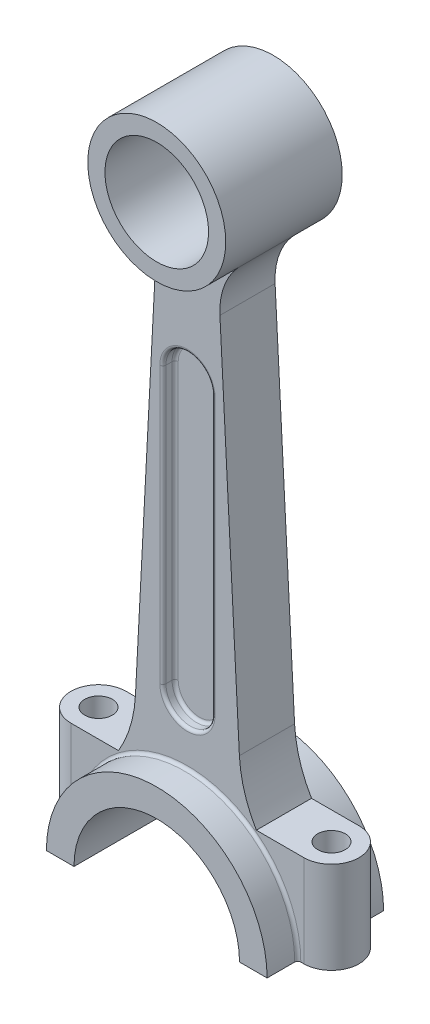
SolidWorks part; units mm, degrees
material "AISI 4340 Steel, normalized"
ref_plane "Front Plane" through (0, 0, 0) normal (0, 0, 1) x (1, 0, 0)
ref_plane "Top Plane" through (0, 0, 0) normal (0, 1, 0) x (1, 0, 0)
ref_plane "Right Plane" through (0, 0, 0) normal (1, 0, 0) x (0, 0, -1)
sketch "Sketch1" plane through (0, 0, 0) normal (0, 0, 1) x (1, 0, 0)
  line L0 (0, -201.2) -> (0, 0) construction
  line L1 (-17.8497, -169.9368) -> (-10, -20.1556)
  line L2 (17.8497, -169.9368) -> (10, -20.1556)
  line L3 (27, -201.2) -> (36, -201.2)
  line L4 (36, -201.2) -> (27, -201.2)
  line L5 (0, -201.2) -> (-36, -201.2)
  circle A4 centre (0, 0) radius 22.5
  circle A5 centre (0, 0) radius 16.9
  arc A6 (27, -201.2) -> (-27, -201.2) centre (0, -201.2) ccw
  arc A7 (36, -201.2) -> (-36, -201.2) centre (0, -201.2) ccw
  dimension "D1" = 33.8
  dimension "D2" = 45
  dimension "D3" = 72
  dimension "D4" = 54
  dimension "D5" = 201.2
  dimension "D6" = 20
  dimension "D7" = 6
extrude "Boss-Extrude1" add sketch "Sketch1" along normal mid plane 38 contours A4 A5 | L0 A6 L3 A7 | A6 L0 A7 L5 region at (-20.1899, -181.0101, 0) region at (20.1899, -181.0101, 0) region at (-4.9903, -21.2865, 0)
extrude "Boss-Extrude2" add sketch "Sketch1<3>" along normal mid plane 18 contours A7 L0 A4 L1 | L0 A7 L2 A4 region at (-7.1843, -100.8455, 0) region at (7.1843, -100.8455, 0)
sketch "Sketch1<3>" plane through (0, 0, 0) normal (0, 0, 1) x (1, 0, 0) same geometry as "Sketch1"
sketch "Sketch2" plane through (0, 0, 9) normal (0, 0, 1) x (1, 0, 0)
  line L0 (0, -55.5604) -> (0, -145.5604) construction
  line L1 (8, -55.5604) -> (8, -145.5604)
  line L2 (-8, -55.5604) -> (-8, -145.5604)
  arc A0 (8, -55.5604) -> (-8, -55.5604) centre (0, -55.5604) ccw
  arc A1 (-8, -145.5604) -> (8, -145.5604) centre (0, -145.5604) ccw
  point P3 (0, -100.5604)
  dimension "D2" = 8
  dimension "D1" = 90
extrude "Cut-Extrude1" cut sketch "Sketch2" against normal blind 4
mirror "Mirror1" about plane through (0, 0, 0) normal (0, 0, 1) of "Cut-Extrude1"
fillet "Fillet2" radius 1 16 edges at (0, -153.5604, 9) (-8, -100.5604, 9) (0, -47.5604, 9) (0, -153.5604, -9) (-8, -100.5604, -9) (0, -47.5604, -9) (8, -100.5604, 5) (0, -153.5604, 5) (-8, -100.5604, 5) (0, -47.5604, 5) (-8, -100.5604, -5) (0, -153.5604, -5) (8, -100.5604, -5) (0, -47.5604, -5) (8, -100.5604, 9) (8, -100.5604, -9)
fillet "Fillet3" radius 22.5 2 edges at (10, -20.1556, 0) (-10, -20.1556, 0)
fillet "Fillet4" radius 40 2 edges at (-17.8497, -169.9368, 0) (17.8497, -169.9368, 0)
ref_plane "Plane2" through (0, -171.2, 0) normal (0, -1, 0) x (-1, 0, 0)
sketch "Sketch3" plane through (0, -171.2, 0) normal (0, -1, 0) x (-1, 0, 0)
  line L0 (38, 0) -> (-38, 0) construction
  line L1 (38, -9) -> (-38, -9)
  line L2 (38, 9) -> (-38, 9)
  arc A0 (38, -9) -> (38, 9) centre (38, 0) ccw
  arc A1 (-38, 9) -> (-38, -9) centre (-38, 0) ccw
  circle A2 centre (-38, 0) radius 4.5
  circle A3 centre (38, 0) radius 4.5
  point P2 (0, 0)
  dimension "D2" = 9
  dimension "D3" = 9
  dimension "D4" = 9
  dimension "D1" = 76
extrude "Boss-Extrude3" add sketch "Sketch3" along normal up to surface (30 mm away) up to face at (-31.5, -201.2, 0)
sketch "Sketch4" plane through (0, 0, -9) normal (0, 0, -1) x (-1, 0, 0)
  line L1 (-27, -201.2) -> (27, -201.2)
  line L2 (-27, -201.2) -> (27, -201.2)
  arc A1 (27, -201.2) -> (-27, -201.2) centre (0, -201.2) ccw
  arc A2 (27, -201.2) -> (-27, -201.2) centre (0, -201.2) ccw
  dimension "D1" = 0
extrude "Cut-Extrude2" cut sketch "Sketch4" against normal through all
fillet "Fillet5" radius 1 2 edges at (0, -165.2, 9) (0, -165.2, -9)
